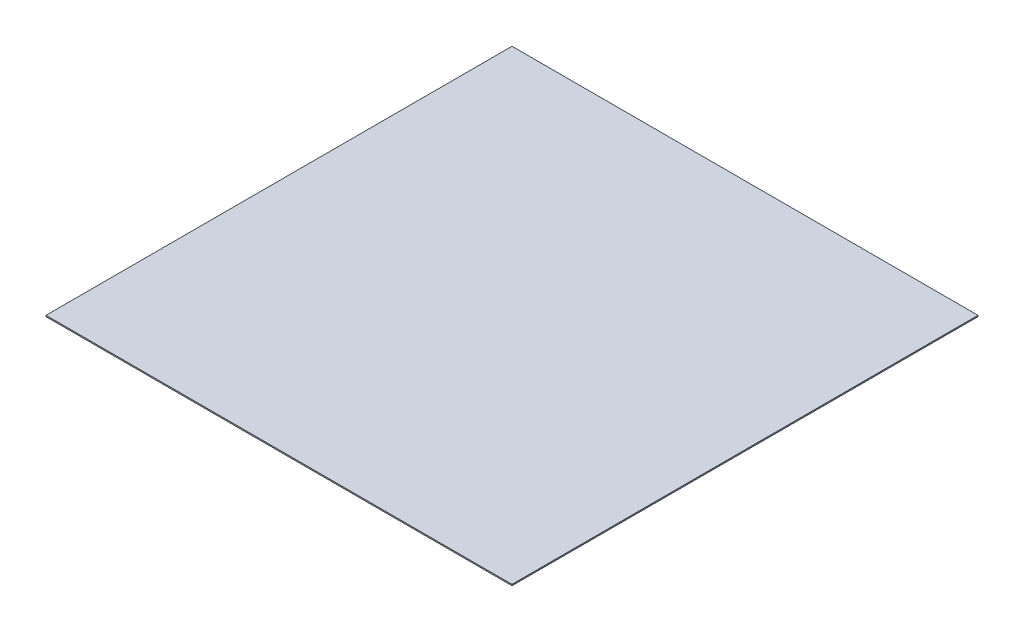
SolidWorks part; units mm, degrees
ref_plane "Front Plane" through (0, 0, 0) normal (0, 0, 1) x (1, 0, 0)
ref_plane "Top Plane" through (0, 0, 0) normal (0, 1, 0) x (1, 0, 0)
ref_plane "Right Plane" through (0, 0, 0) normal (1, 0, 0) x (0, 0, -1)
sketch "Sketch1" plane through (0, 0, 0) normal (0, 0, 1) x (1, 0, 0)
  line L0 (0, 0.3969) -> (0, -0.3969)
  line L1 (-152.4, 0) -> (152.4, 0) construction
  point P6 (0, 0)
  dimension "Width" = 304.8
  dimension "Thk" = 0.7937
sketch "Sketch2" plane through (0, 0, 0) normal (1, 0, 0) x (0, 0, -1)
  line L0 (152.4, 0) -> (-152.4, 0)
  point P4 (0, 0)
  dimension "Length" = 304.8
sketch "Sketch3" plane through (0, 0, 0) normal (0, 0, 1) x (1, 0, 0)
  line L1 (152.4, 0.3969) -> (-152.4, 0.3969)
  line L2 (152.4, 0.3969) -> (152.4, -0.3969)
  line L3 (152.4, -0.3969) -> (-152.4, -0.3969)
  line L4 (-152.4, 0.3969) -> (-152.4, -0.3969)
  line L5 (152.4, 0.3969) -> (-152.4, -0.3969) construction
  line L6 (152.4, -0.3969) -> (-152.4, 0.3969) construction
  point P0 (0, 0)
extrude "Boss-Extrude1" add sketch "Sketch3" along normal up to vertex (152.4 mm away) and the other way up to vertex (152.4 mm away) up to point (0, 0, 152.4) other way up to point (0, 0, -152.4)
